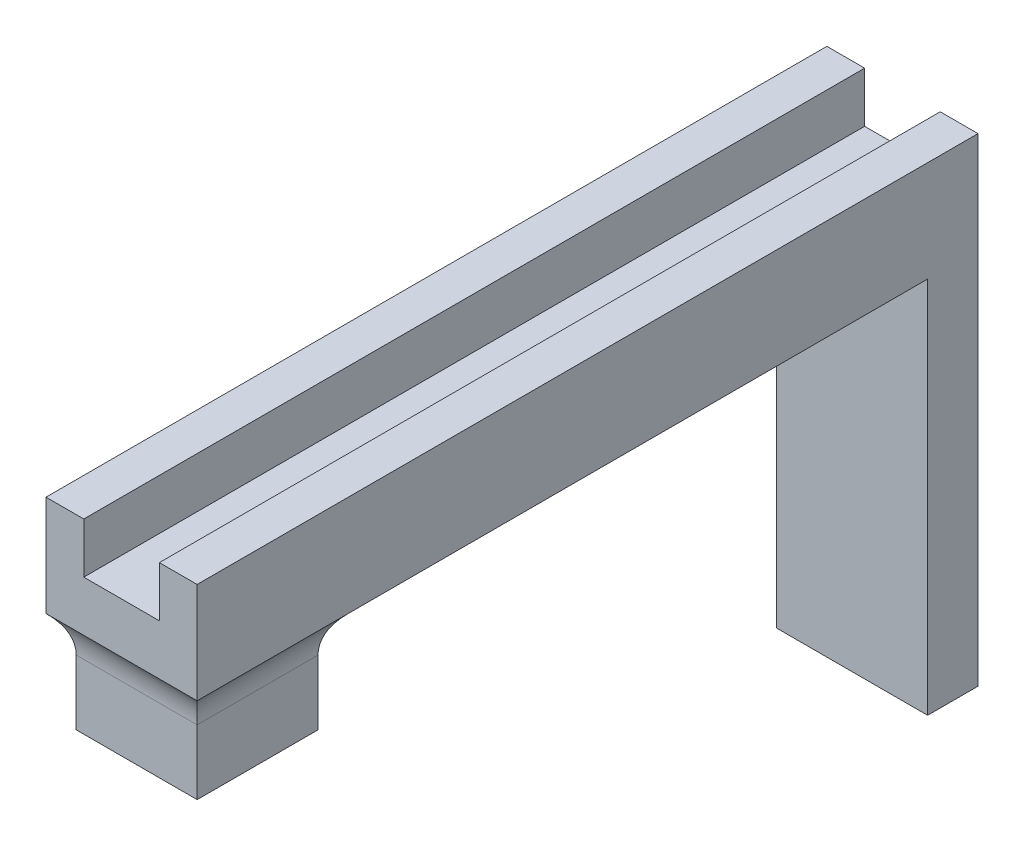
SolidWorks part; units mm, degrees
ref_plane "Front Plane" through (0, 0, 0) normal (0, 0, 1) x (1, 0, 0)
ref_plane "Top Plane" through (0, 0, 0) normal (0, 1, 0) x (1, 0, 0)
ref_plane "Right Plane" through (0, 0, 0) normal (1, 0, 0) x (0, 0, -1)
sketch "Sketch1" plane through (0, 0, 0) normal (0, 1, 0) x (1, 0, 0)
  line L1 (0, 0) -> (6.096, 0)
  line L2 (0, 0) -> (0, 6.096)
  line L3 (0, 6.096) -> (6.096, 6.096)
  line L4 (6.096, 0) -> (6.096, 6.096)
  dimension "D1" = 6.096
  dimension "D2" = 6.096
extrude "Boss-Extrude1" add sketch "Sketch1" along normal blind 5.08
sketch "Sketch2" plane through (0, 5.08, 0) normal (0, 1, 0) x (1, 0, 0)
  line L0 (6.096, 6.096) -> (0, 6.096) construction
  line L1 (-0.762, 6.858) -> (6.858, 6.858)
  line L2 (-0.762, 6.858) -> (-0.762, -0.762)
  line L3 (-0.762, -0.762) -> (6.858, -0.762)
  line L4 (6.858, 6.858) -> (6.858, -0.762)
  line L6 (0, 6.096) -> (0, 0) construction
  dimension "D1" = 7.62
  dimension "D2" = 7.62
  dimension "D3" = 0.762
  dimension "D4" = 0.762
extrude "Boss-Extrude2" add sketch "Sketch2" along normal blind 5.08
fillet "Fillet1" radius 2.54 1 edges at (0, 5.08, -3.048)
fillet "Fillet2" radius 2.54 3 edges at (2.667, 5.08, 0) (6.096, 5.08, -3.048) (2.667, 5.08, -6.096)
sketch "Sketch4" plane through (0, 0, -6.858) normal (0, 0, -1) x (-1, 0, 0)
  line L1 (-6.858, 10.16) -> (0.762, 10.16)
  line L2 (-6.858, 10.16) -> (-6.858, 5.08)
  line L3 (-6.858, 5.08) -> (0.762, 5.08)
  line L4 (0.762, 10.16) -> (0.762, 5.08)
extrude "Boss-Extrude4" add sketch "Sketch4" along normal blind 31.75
sketch "Sketch5" plane through (0, 10.16, 0) normal (0, 1, 0) x (1, 0, 0)
  line L0 (-0.762, 38.608) -> (6.858, 38.608) construction
  line L1 (1.143, 38.608) -> (4.953, 38.608)
  line L2 (1.143, 38.608) -> (1.143, -0.762)
  line L3 (1.143, -0.762) -> (4.953, -0.762)
  line L4 (4.953, 38.608) -> (4.953, -0.762)
  line L5 (-0.762, -0.762) -> (6.858, -0.762) construction
  line L6 (6.858, -0.762) -> (6.858, 38.608) construction
  dimension "D1" = 1.905
  dimension "D2" = 3.81
extrude "Cut-Extrude1" cut sketch "Sketch5" against normal blind 2.54
sketch "Sketch7" plane through (0, 5.08, 0) normal (0, -1, 0) x (1, 0, 0)
  line L0 (6.858, -38.608) -> (6.858, -6.858) construction
  line L1 (-0.762, -38.608) -> (6.858, -38.608)
  line L2 (-0.762, -38.608) -> (-0.762, -36.068)
  line L3 (-0.762, -36.068) -> (6.858, -36.068)
  line L4 (6.858, -38.608) -> (6.858, -36.068)
  dimension "D1" = 2.54
  dimension "D2" = 7.62
extrude "Boss-Extrude5" add sketch "Sketch7" along normal blind 19.05
